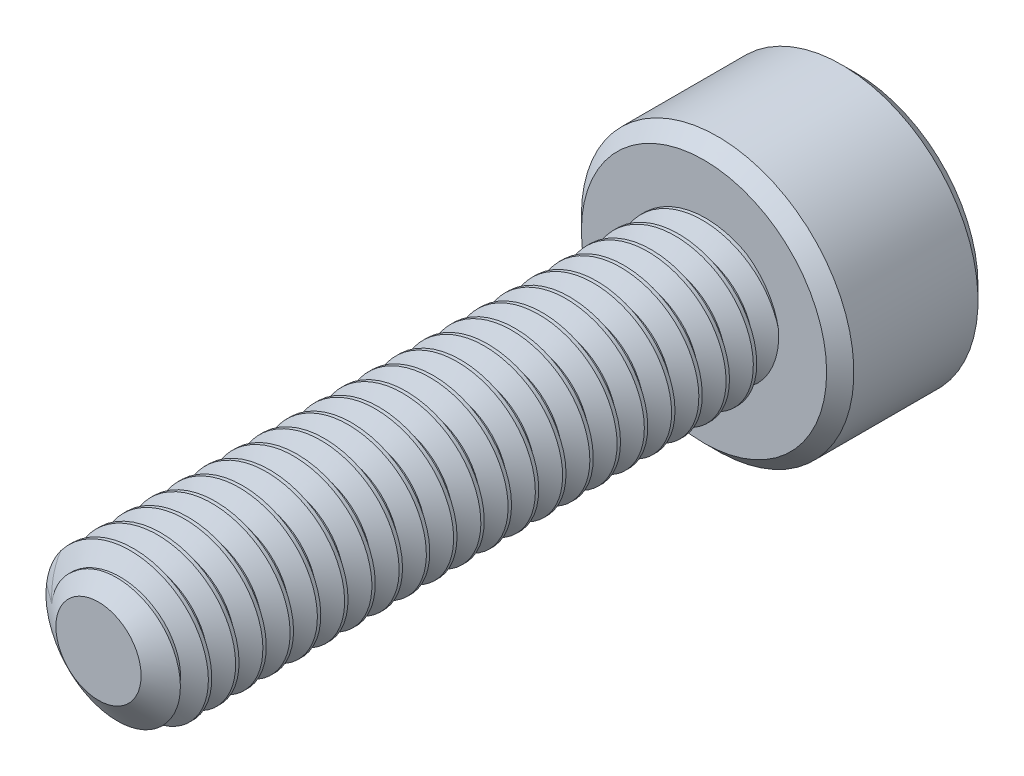
SolidWorks part; units mm, degrees
other "DetailItem1"
ref_plane "Front Plane" through (0, 0, 0) normal (0, 0, 1) x (1, 0, 0)
ref_plane "Top Plane" through (0, 0, 0) normal (0, 1, 0) x (1, 0, 0)
ref_plane "Right Plane" through (0, 0, 0) normal (1, 0, 0) x (0, 0, -1)
sketch "Sketch1" plane through (0, 0, 0) normal (0, 0, 1) x (1, 0, 0)
  circle A0 centre (0, 0) radius 1.25
  dimension "OD" = 2.5
extrude "Extrude1" add sketch "Sketch1" against normal blind 10
sketch "Sketch2" plane through (0, 0, 0) normal (0, 0, 1) x (1, 0, 0)
  circle A0 centre (0, 0) radius 1.25 construction
  circle A1 centre (0, 0) radius 1.25
curve "Helix/Spiral1" pitch 0.45 height 10.45 radius 1.25 centre (0, 0, 0) axis (0, 0, -1) start towards (0, 1, 0) parameters "pitch"=0.45
sketch "Sketch3" plane through (0, 0, 0) normal (1, 0, 0) x (0, 0, -1)
  line L0 (-0.3937, 1.25) -> (-0.225, 0.9577)
  line L1 (-0.225, 0.9577) -> (-0.1688, 0.9577)
  line L2 (-0.1688, 0.9577) -> (0, 1.25)
  line L3 (-0.3937, 1.25) -> (0, 1.25)
  line L4 (-0.1969, 1.25) -> (-0.1969, 0.9577) construction
  line L5 (-0.3094, 1.1039) -> (-0.0844, 1.1039) construction
  line L6 (0, 1.25) -> (0, -1.25) construction
  dimension "D1" = 0.0563
  dimension "D2" = 0.225
  dimension "D3" = 60
sweep "Cut-Sweep1" cut profiles "Sketch3" path "Helix/Spiral1" align with end faces yes
sketch "Sketch4" plane through (0, 0, 0) normal (1, 0, 0) x (0, 0, -1)
  line L0 (0.3825, 1.25) -> (0, 0.7037)
  line L1 (0, 0.7037) -> (0, 1.25)
  line L2 (0.3825, 1.25) -> (0, 1.25)
  line L3 (-0.3937, 1.25) -> (0, 1.25) construction
  line L4 (0, 0) -> (7.0209, 0) construction
  dimension "D1" = 55
  dimension "D2" = 0.254
revolve "Cut-Revolve1" cut sketch "Sketch4" angle 360 about L4
sketch "Sketch6" plane through (0, 0, -10) normal (0, 0, -1) x (-1, 0, 0)
  circle A0 centre (0, 0) radius 2.25
  dimension "head dia" = 4.5
extrude "Extrude2" add sketch "Sketch6" along normal blind 2.5
sketch "Sketch7" plane through (0, 0, -12.5) normal (0, 0, -1) x (-1, 0, 0)
  line L1 (0, 1.1547) -> (-1, 0.5774)
  line L2 (-1, 0.5774) -> (-1, -0.5774)
  line L3 (-1, -0.5774) -> (0, -1.1547)
  line L4 (0, -1.1547) -> (1, -0.5774)
  line L5 (1, -0.5774) -> (1, 0.5774)
  line L6 (1, 0.5774) -> (0, 1.1547)
  circle A0 centre (0, 0) radius 1 construction
  dimension "hex dia" = 2
extrude "Cut-Extrude1" cut sketch "Sketch7" against normal blind 1.5
sketch "Sketch8" plane through (0, 0, -12.5) normal (0, 0, -1) x (-1, 0, 0)
  circle A0 centre (0, 0) radius 1.1547
extrude "Cut-Extrude2" cut sketch "Sketch8" against normal through all draft 45
chamfer "Chamfer1" distance 0.225 angle 45 2 edges at (-2.25, 0, -12.5) (-2.25, 0, -10)
sketch "Sketch10" plane through (0, 0, -10) normal (0, 0, 1) x (1, 0, 0)
  circle A1 centre (0, 0) radius 1.25
  circle A2 centre (0, 0) radius 1.25
  dimension "D1" = 0
ref_plane "Plane1" through (0, 0, 0) normal (0, 0, 1) x (1, 0, 0)
extrude "partial thread" [suppressed] add sketch "Sketch10" along normal up to surface (8 mm away) separate body up to plane "Plane1"
chamfer "Chamfer2" [suppressed] distance 0.05 angle 45
combine bodies "Combine1" [suppressed] operation type add bodies to combine 107 108
sketch "Sketch9" plane through (0, 0, 0) normal (1, 0, 0) x (0, 0, -1)
  line L0 (0, 1.25) -> (0, -1.25) construction
  line L1 (1.125, 1.25) -> (1.125, -1.25) construction
  dimension "D1" = 1.125
equation "\"D3@Helix/Spiral1\" = \"screw length@Extrude1\"+\"pitch@Helix/Spiral1\""
equation "\"D1@Sketch3\" = \"pitch@Helix/Spiral1\"*.125"
equation "\"D2@Sketch3\" = \"pitch@Helix/Spiral1\"*.5"
equation "\"D1@Cut-Extrude1\" = \"hex dia@Sketch7\"*.75"
equation "\"D1@Chamfer1\" = \"head dia@Sketch6\"*.05"
equation "\"D1@Sketch9\" = \"pitch@Helix/Spiral1\"*2.5"
equation "\"D1@Chamfer2\"=\"OD@Sketch1\"*.02"
